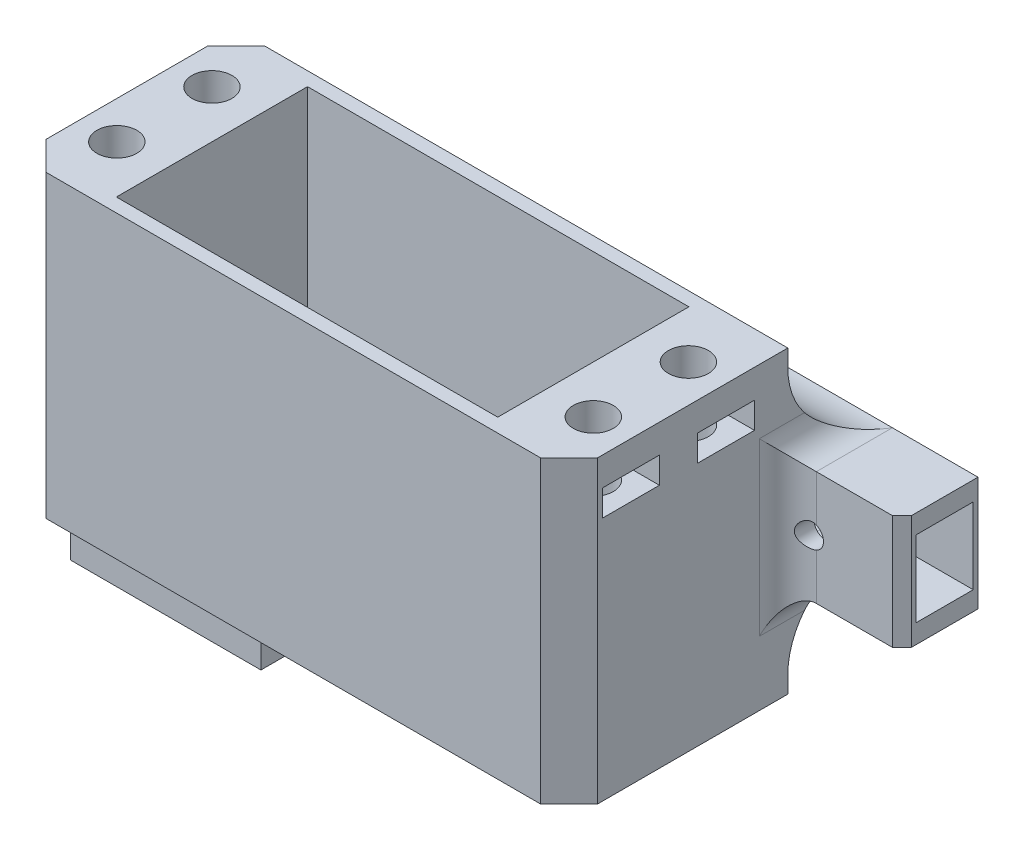
SolidWorks part; units mm, degrees
ref_plane "Front Plane" through (0, 0, 0) normal (0, 0, 1) x (1, 0, 0)
ref_plane "Top Plane" through (0, 0, 0) normal (0, 1, 0) x (1, 0, 0)
ref_plane "Right Plane" through (0, 0, 0) normal (1, 0, 0) x (0, 0, -1)
sketch "Sketch1" plane through (0, 0, 0) normal (0, 1, 0) x (1, 0, 0)
  line L0 (9.9, 0.4273) -> (50, 0.4273)
  line L1 (50, 0.4273) -> (50, -19.6727)
  line L2 (50, -19.6727) -> (9.9, -19.6727)
  line L4 (0.95, -21.1227) -> (58.95, -21.1227)
  line L5 (58.95, -21.1227) -> (58.95, 1.8773)
  line L6 (58.95, 1.8773) -> (0.95, 1.8773)
  line L8 (55, -4.6227) -> (55, -14.6227) construction
  line L9 (0.95, 1.8773) -> (0.95, -21.1227)
  line L10 (9.9, 0.4273) -> (9.9, -19.6727)
  line L11 (29.95, 0.4273) -> (29.95, -19.6727) construction
  circle A0 centre (55, -4.6227) radius 2.1
  circle A1 centre (55, -14.6227) radius 2.1
  circle A2 centre (4.9, -14.6227) radius 2.1
  circle A3 centre (4.9, -4.6227) radius 2.1
  point P13 (55, -9.6227)
  point P14 (50, -9.6227)
  point P20 (0.95, -9.6227)
  point P22 (29.95, 1.8773)
  dimension "D1" = 4.2
  dimension "D2" = 10
  dimension "D3" = 23
  dimension "D4" = 40.1
  dimension "D5" = 5
  dimension "D6" = 20.1
  dimension "D7" = 58
extrude "Boss-Extrude1" add sketch "Sketch1" along normal blind 28.35
sketch "Sketch11" plane through (0, 0, 0) normal (0, -1, 0) x (1, 0, 0)
  line L1 (0.95, 21.1227) -> (58.95, 21.1227)
  line L2 (0.95, 21.1227) -> (0.95, -1.8773)
  line L3 (0.95, -1.8773) -> (58.95, -1.8773)
  line L4 (58.95, 21.1227) -> (58.95, -1.8773)
extrude "Boss-Extrude5" add sketch "Sketch11" along normal blind 3.175
sketch "Sketch14" plane through (0, 0, -1.8773) normal (0, 0, -1) x (-1, 0, 0)
  line L7 (-58.95, 28.35) -> (-58.95, -3.175) construction
  line L8 (-46.95, 6.5875) -> (-70.95, 6.5875)
  line L9 (-46.95, 6.5875) -> (-46.95, 18.5875)
  line L10 (-46.95, 18.5875) -> (-70.95, 18.5875)
  line L11 (-70.95, 6.5875) -> (-70.95, 18.5875)
  line L12 (-46.95, 6.5875) -> (-70.95, 18.5875) construction
  line L13 (-46.95, 18.5875) -> (-70.95, 6.5875) construction
  point P0 (-58.95, 12.5875)
  point P5 (-58.95, 12.5875)
  dimension "D1" = 24
  dimension "D2" = 12
  dimension "D3" = 0
extrude "Boss-Extrude7" add sketch "Sketch14" along normal blind 9
ref_plane "Plane1" through (0, 0, -6.3773) normal (0, 0, 1) x (1, 0, 0)
sketch "Sketch16" plane through (0, 0, -6.3773) normal (0, 0, 1) x (1, 0, 0)
  line L0 (70.95, 18.5875) -> (70.95, 6.5875) construction
  line L1 (57.45, 8.5875) -> (70.95, 8.5875)
  line L3 (57.45, 16.5875) -> (70.95, 16.5875)
  line L4 (70.95, 8.5875) -> (70.95, 16.5875)
  line L5 (46.95, 6.5875) -> (46.95, 18.5875) construction
  arc A0 (57.45, 16.5875) -> (57.45, 8.5875) centre (57.45, 12.5875) ccw
  point P9 (46.95, 12.5875)
  dimension "D2" = 4
  dimension "D1" = 13.5
extrude "Cut-Extrude1" cut sketch "Sketch16" against normal mid plane 6
sketch "Sketch18" plane through (0, 0, -10.8773) normal (0, 0, -1) x (-1, 0, 0)
  arc A0 (-60.2, 12.5875) -> (-62.7, 12.5875) centre (-61.45, 12.5875) ccw construction
  arc A1 (-62.7, 12.5875) -> (-60.2, 12.5875) centre (-61.45, 12.5875) ccw construction
  arc A2 (-56.2, 12.5875) -> (-58.7, 12.5875) centre (-57.45, 12.5875) ccw construction
  arc A3 (-58.7, 12.5875) -> (-56.2, 12.5875) centre (-57.45, 12.5875) ccw construction
  arc A4 (-60.2, 12.5875) -> (-62.7, 12.5875) centre (-61.45, 12.5875) ccw
  arc A5 (-62.7, 12.5875) -> (-60.2, 12.5875) centre (-61.45, 12.5875) ccw
  arc A6 (-56.2, 12.5875) -> (-58.7, 12.5875) centre (-57.45, 12.5875) ccw
  arc A7 (-58.7, 12.5875) -> (-56.2, 12.5875) centre (-57.45, 12.5875) ccw
extrude "Cut-Extrude2" cut sketch "Sketch18" against normal up to surface (9 mm away) up to face at (64.95, 12.5875, -1.8773)
fillet "Fillet1" radius 8 3 edges at (52.95, 6.5875, -1.8773) (46.95, 12.5875, -1.8773) (52.95, 18.5875, -1.8773)
chamfer "Chamfer2" distance 3 angle 45 3 edges at (0.95, 12.5875, -1.8773) (0.95, 12.5875, 21.1227) (58.95, 12.5875, 21.1227)
fillet "Fillet2" radius 3 2 edges at (58.95, 6.5875, -5.8773) (58.95, 18.5875, -5.8773)
fillet "Fillet3" radius 3 1 edges at (58.95, 12.5875, -1.8773)
chamfer "Chamfer3" distance 1 angle 45 5 edges at (70.95, 12.5875, -1.8773) (70.95, 12.5875, -10.8773) (58.95, 6.5875, -10.8773) (46.95, 12.5875, -10.8773) (58.95, 18.5875, -10.8773)
ref_plane "Plane2" through (0, 25.35, 0) normal (0, 1, 0) x (1, 0, 0)
sketch "Sketch19" plane through (0, 25.35, 0) normal (0, 1, 0) x (1, 0, 0)
  line L0 (0.95, -1.1227) -> (0.95, -18.1227) construction
  line L1 (0.95, -1.6227) -> (8.95, -1.6227)
  line L2 (0.95, -1.6227) -> (0.95, -7.6227)
  line L3 (0.95, -7.6227) -> (8.95, -7.6227)
  line L4 (8.95, -1.6227) -> (8.95, -7.6227)
  line L5 (-0.5892, -9.6227) -> (60.8708, -9.6227) construction
  line L6 (29.95, -22.0073) -> (29.95, 3.0189) construction
  line L7 (9.9, 0.4273) -> (9.9, -19.6727) construction
  line L8 (50, 0.4273) -> (9.9, 0.4273) construction
  line L9 (8.95, -17.6227) -> (8.95, -11.6227)
  line L10 (0.95, -11.6227) -> (8.95, -11.6227)
  line L11 (0.95, -17.6227) -> (0.95, -11.6227)
  line L12 (0.95, -17.6227) -> (8.95, -17.6227)
  line L37 (60.4892, -9.6227) -> (-0.9708, -9.6227) construction
  line L38 (58.95, -17.6227) -> (50.95, -17.6227)
  line L39 (58.95, -17.6227) -> (58.95, -11.6227)
  line L40 (58.95, -11.6227) -> (50.95, -11.6227)
  line L41 (50.95, -17.6227) -> (50.95, -11.6227)
  line L42 (50.95, -1.6227) -> (50.95, -7.6227)
  line L43 (58.95, -7.6227) -> (50.95, -7.6227)
  line L44 (58.95, -1.6227) -> (58.95, -7.6227)
  line L45 (58.95, -1.6227) -> (50.95, -1.6227)
  circle A0 centre (4.9, -4.6227) radius 2.1 construction
  circle A1 centre (4.9, -4.6227) radius 2.1 construction
  circle A2 centre (4.9, -14.6227) radius 2.1 construction
  circle A3 centre (4.9, -4.6227) radius 2.1 construction
  circle A4 centre (4.9, -14.6227) radius 2.1 construction
  circle A5 centre (4.9, -4.6227) radius 2.1 construction
  circle A6 centre (4.9, -14.6227) radius 2.1 construction
  circle A7 centre (4.9, -4.6227) radius 2.1 construction
  circle A8 centre (4.9, -14.6227) radius 2.1 construction
  circle A9 centre (55, -14.6227) radius 2.1 construction
  circle A10 centre (55, -4.6227) radius 2.1 construction
  circle A11 centre (55, -14.6227) radius 2.1 construction
  circle A12 centre (55, -4.6227) radius 2.1 construction
  circle A13 centre (55, -14.6227) radius 2.1 construction
  circle A14 centre (55, -4.6227) radius 2.1 construction
  circle A15 centre (55, -14.6227) radius 2.1 construction
  circle A16 centre (55, -4.6227) radius 2.1 construction
  point P11 (0.95, -4.6227)
  point P18 (9.9, -9.6227)
  point P21 (29.95, 0.4273)
  point P28 (0.95, -14.6227)
  point P55 (58.95, -14.6227)
  point P56 (58.95, -4.6227)
  dimension "D1" = 6
  dimension "D2" = 8
extrude "Cut-Extrude3" cut sketch "Sketch19" against normal blind 2.75
sketch "Sketch20" plane through (0, 0, 0) normal (0, 1, 0) x (1, 0, 0)
  line L0 (0.95, -1.1227) -> (0.95, -18.1227) construction
  line L1 (0.95, -12.1227) -> (9.9, -12.1227)
  line L2 (0.95, -12.1227) -> (0.95, -7.1227)
  line L3 (0.95, -7.1227) -> (9.9, -7.1227)
  line L4 (9.9, -12.1227) -> (9.9, -7.1227)
  line L5 (9.9, 0.4273) -> (9.9, -19.6727) construction
  point P6 (0.95, -9.6227)
  dimension "D1" = 5
extrude "Cut-Extrude4" cut sketch "Sketch20" along normal blind 3.5
sketch "Sketch21" plane through (0, -3.175, 0) normal (0, -1, 0) x (1, 0, 0)
  line L0 (0.95, 18.1227) -> (0.95, 1.1227) construction
  line L1 (25.05, -0.3773) -> (5.05, -0.3773)
  line L2 (25.05, -0.3773) -> (25.05, 19.6227)
  line L3 (25.05, 19.6227) -> (5.05, 19.6227)
  line L4 (5.05, -0.3773) -> (5.05, 19.6227)
  line L5 (25.05, -0.3773) -> (5.05, 19.6227) construction
  line L6 (25.05, 19.6227) -> (5.05, -0.3773) construction
  point P0 (15.05, 9.6227)
  point P7 (0.95, 9.6227)
  point P8 (0, 0)
  dimension "D1" = 14.1
  dimension "D2" = 20
  dimension "D3" = 20
extrude "Boss-Extrude8" add sketch "Sketch21" along normal blind 6
sketch "Sketch13" plane through (0, -9.175, 0) normal (0, -1, 0) x (1, 0, 0)
  line L0 (0.95, 18.1227) -> (0.95, 1.1227) construction
  circle A0 centre (15.05, 9.6227) radius 3
  point P2 (0.95, 9.6227)
  dimension "D2" = 6
  dimension "D1" = 14.1
extrude "Boss-Extrude6" add sketch "Sketch13" along normal blind 5
fillet "Fillet4" radius 1 4 edges at (15.05, -3.175, 19.6227) (25.05, -3.175, 9.6227) (15.05, -3.175, -0.3773) (5.05, -3.175, 9.6227)
chamfer "Chamfer4" distance 2 angle 45 4 edges at (15.05, -9.175, 19.6227) (25.05, -9.175, 9.6227) (15.05, -9.175, -0.3773) (5.05, -9.175, 9.6227)
